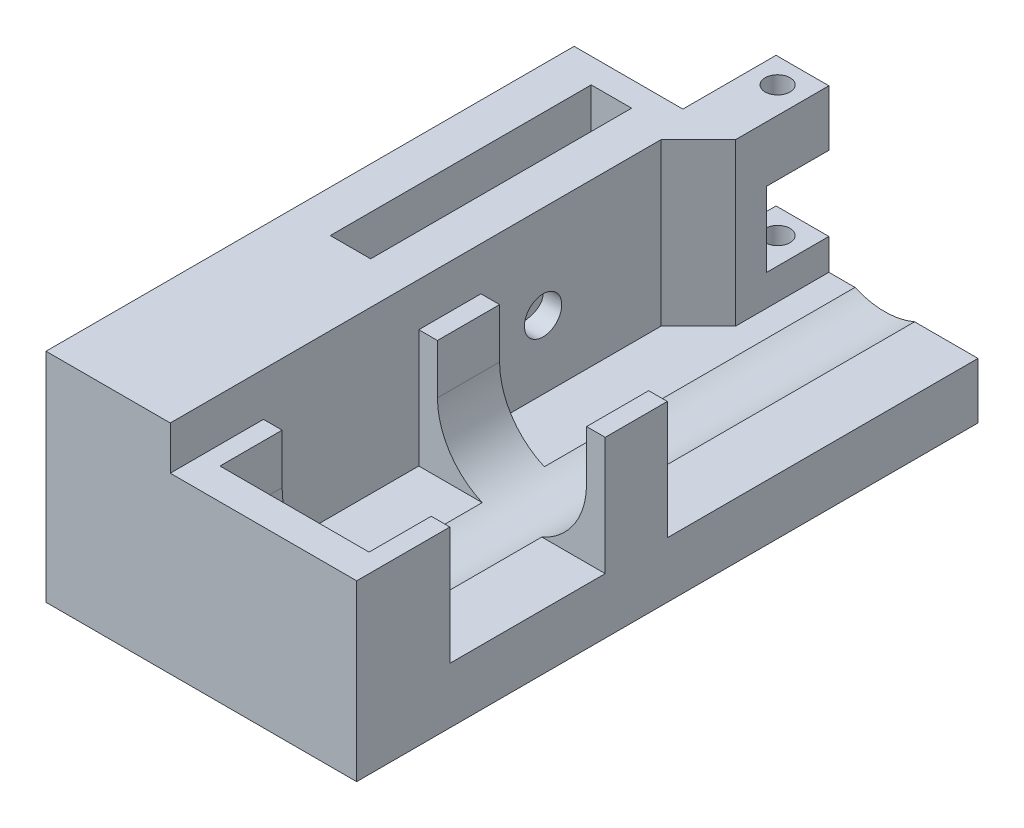
SolidWorks part; units mm, degrees
ref_plane "Front Plane" through (0, 0, 0) normal (0, 0, 1) x (1, 0, 0)
ref_plane "Top Plane" through (0, 0, 0) normal (0, 1, 0) x (1, 0, 0)
ref_plane "Right Plane" through (0, 0, 0) normal (1, 0, 0) x (0, 0, -1)
sketch "Sketch1" plane through (0, 0, 0) normal (0, 0, 1) x (1, 0, 0)
  line L5 (-10, -15) -> (10, -15)
  line L6 (-10, -15) -> (-10, 15)
  line L7 (-10, 15) -> (10, 15)
  line L8 (10, -15) -> (10, 15)
  line L9 (-10, -15) -> (10, 15) construction
  line L10 (-10, 15) -> (10, -15) construction
  point P0 (0, 0)
  dimension "D1" = 20
  dimension "D2" = 30
extrude "Boss-Extrude1" add sketch "Sketch1" along normal blind 85
sketch "Sketch3" plane through (0, 0, 0) normal (0, 0, 1) x (1, 0, 0)
  circle A0 centre (0, 0) radius 7
  dimension "D1" = 14
extrude "Cut-Extrude1" cut sketch "Sketch3" along normal blind 75
sketch "Sketch4" plane through (-10, 0, 0) normal (-1, 0, 0) x (0, 0, 1)
  circle A0 centre (25, 0) radius 3
  dimension "D1" = 25
  dimension "D2" = 6
  dimension "D3" = 0
extrude "Cut-Extrude2" cut sketch "Sketch4" against normal through all
sketch "Sketch5" plane through (0, 15, 0) normal (0, 1, 0) x (1, 0, 0)
  line L1 (-3.25, -46) -> (3.25, -46)
  line L2 (-3.25, -46) -> (-3.25, -4)
  line L3 (-3.25, -4) -> (3.25, -4)
  line L4 (3.25, -46) -> (3.25, -4)
  line L5 (-3.25, -46) -> (3.25, -4) construction
  line L6 (-3.25, -4) -> (3.25, -46) construction
  point P0 (0, -25)
  dimension "D1" = 25
  dimension "D2" = 42
  dimension "D3" = 0
  dimension "D4" = 6.5
extrude "Cut-Extrude3" cut sketch "Sketch5" against normal through all
sketch "Sketch6" plane through (10, 0, 0) normal (1, 0, 0) x (0, 0, -1)
  line L0 (-85, -15) -> (-85, 15) construction
  line L1 (0, -15) -> (-85, -15)
  line L2 (0, -15) -> (0, -11)
  line L3 (0, -11) -> (-85, -11)
  line L4 (-85, -15) -> (-85, -11)
  dimension "D1" = 4
extrude "Boss-Extrude2" add sketch "Sketch6" along normal blind 30
sketch "Sketch7" plane through (0, 0, 85) normal (0, 0, 1) x (1, 0, 0)
  line L0 (10, -11) -> (10, 15) construction
  line L3 (40, 0) -> (40, -11)
  line L5 (10, -11) -> (40, -11)
  line L8 (13, 0) -> (13, 8)
  line L9 (13, 8) -> (10, 8)
  line L24 (40, 0) -> (40, 8)
  line L25 (40, 8) -> (37, 8)
  line L26 (37, 0) -> (37, 8)
  line L27 (10, -11) -> (10, 8)
  line L28 (10, -11) -> (10, 8)
  arc A0 (13, 0) -> (37, 0) centre (25, 0) ccw
  line M4 (40, -11) -> (10, -11)
  line M5 (10, -11) -> (10, 15)
  dimension "D1" = 24
  dimension "D2" = 15
  dimension "D3" = 0
  dimension "D4" = 3
  dimension "D6" = 8
  dimension "D7" = 8
extrude "Boss-Extrude3" add sketch "Sketch7" against normal blind 15 contours A0 M5 M4 | A0 L3 M4 region at (12.4717, -3.4409, 85) region at (37.5283, -3.4409, 85)
sketch "Sketch8" plane through (0, 0, 85) normal (0, 0, 1) x (1, 0, 0)
  circle A0 centre (25, 0) radius 12
  dimension "D1" = 24
extrude "Cut-Extrude4" cut sketch "Sketch8" against normal through all
sketch "Sketch9" plane through (0, 0, 85) normal (0, 0, 1) x (1, 0, 0)
  line L1 (10, 8) -> (40, 8)
  line L2 (10, 8) -> (10, -15)
  line L3 (10, -15) -> (40, -15)
  line L4 (40, 8) -> (40, -15)
extrude "Boss-Extrude4" add sketch "Sketch9" against normal blind 5
extrude "Boss-Extrude5" add sketch "Sketch7<3>" against normal blind 10 from offset 40 contours A0 L3 L24 L25 L26 M4 | A0 L8 L9 M5 M4 region at (12.4717, -3.4409, 85) region at (37.5283, -3.4409, 85) offset against normal yes
sketch "Sketch7<3>" plane through (0, 0, 85) normal (0, 0, 1) x (1, 0, 0) same geometry as "Sketch7"
sketch "Sketch10" plane through (0, -15, 0) normal (0, -1, 0) x (1, 0, 0)
  line L8 (40, 0) -> (40, 85)
  line L9 (40, 85) -> (-10, 85)
  line L10 (-10, 85) -> (-10, 0)
  line L11 (-10, 0) -> (40, 0)
  line L12 (40, 0) -> (40, 85)
  line L13 (40, 85) -> (-10, 85)
  line L14 (-10, 85) -> (-10, 0)
  line L15 (-10, 0) -> (40, 0)
  line L26 (-3.25, 4) -> (3.25, 4)
  line L27 (-3.25, 46) -> (-3.25, 4)
  line L28 (3.25, 4) -> (3.25, 46)
  line L29 (3.25, 46) -> (-3.25, 46)
  line L30 (-3.25, 4) -> (3.25, 4)
  line L31 (-3.25, 46) -> (-3.25, 4)
  line L32 (3.25, 4) -> (3.25, 46)
  line L33 (3.25, 46) -> (-3.25, 46)
  dimension "D1" = 0
  dimension "D2" = 0
extrude "Boss-Extrude6" add sketch "Sketch10" along normal blind 5
sketch "Sketch11" plane through (0, 0, 0) normal (0, 0, -1) x (-1, 0, 0)
  line L7 (-10, -11) -> (10, -11)
  line L14 (-29.7958, -11) -> (-40, -11)
  line L15 (-40, -11) -> (-40, -20)
  line L16 (-40, -20) -> (10, -20)
  line L17 (10, -20) -> (10, 15)
  line L18 (10, 15) -> (-10, 15)
  line L19 (-10, 15) -> (-10, -11)
  line L20 (-10, -11) -> (-20.2042, -11)
  line L21 (-29.7958, -11) -> (-40, -11)
  line L22 (-40, -11) -> (-40, -20)
  line L23 (-40, -20) -> (10, -20)
  line L24 (10, -20) -> (10, -11)
  line L27 (-10, -11) -> (-20.2042, -11)
  arc A2 (-29.7958, -11) -> (-20.2042, -11) centre (-25, 0) ccw
  arc A3 (-29.7958, -11) -> (-20.2042, -11) centre (-25, 0) ccw
  dimension "D1" = 0
extrude "Boss-Extrude7" add sketch "Sketch11" along normal blind 15
sketch "Sketch12" plane through (0, -11, 0) normal (0, 1, 0) x (1, 0, 0)
  line L0 (10, 0) -> (-10, 0) construction
  line L1 (7.5, 0) -> (10, 0)
  line L2 (7.5, 0) -> (7.5, 15)
  line L3 (7.5, 15) -> (16, 15)
  line L4 (16, 0) -> (16, 15)
  line L5 (-10, 15) -> (20.2042, 15) construction
  line L6 (-10, 15) -> (-10, 0) construction
  line L10 (16, 0) -> (10, -6)
  line L11 (10, -85) -> (10, 0) construction
  line L12 (10, -6) -> (10, 0)
  dimension "D1" = 17.5
  dimension "D2" = 8.5
  dimension "D3" = 6
  dimension "D4" = 15
extrude "Boss-Extrude8" add sketch "Sketch12" along normal up to surface (26 mm away) up to face at (0, 15, 25)
sketch "Sketch13" plane through (0, 0, -15) normal (0, 0, -1) x (-1, 0, 0)
  line L0 (-16, 15) -> (-16, -11) construction
  line L1 (-16, 6) -> (-7.5, 6)
  line L2 (-16, 6) -> (-16, -6)
  line L3 (-16, -6) -> (-7.5, -6)
  line L4 (-7.5, 6) -> (-7.5, -6)
  line L5 (-7.5, 15) -> (-7.5, -11) construction
  dimension "D1" = 6
  dimension "D2" = 6
extrude "Cut-Extrude5" cut sketch "Sketch13" against normal blind 10
sketch "Sketch14" plane through (0, 15, 0) normal (0, 1, 0) x (1, 0, 0)
  line L0 (7.5, 15) -> (16, 15) construction
  line L1 (7.5, 0) -> (7.5, 15) construction
  circle A0 centre (11.75, 11) radius 2
  dimension "D1" = 4
  dimension "D2" = 4
  dimension "D3" = 4.25
extrude "Cut-Extrude6" cut sketch "Sketch14" against normal blind 25
